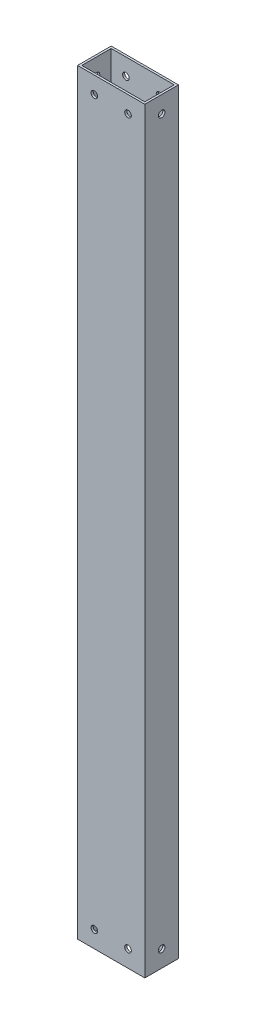
SolidWorks part; units mm, degrees
material "6061-T6 (SS)"
ref_plane "Front Plane" through (0, 0, 0) normal (0, 0, 1) x (1, 0, 0)
ref_plane "Top Plane" through (0, 0, 0) normal (0, 1, 0) x (1, 0, 0)
ref_plane "Right Plane" through (0, 0, 0) normal (1, 0, 0) x (0, 0, -1)
sketch "Sketch1" plane through (0, 0, 0) normal (0, 0, 1) x (1, 0, 0)
  line L1 (-25.4, -285.75) -> (25.4, -285.75)
  line L2 (-25.4, -285.75) -> (-25.4, 285.75)
  line L3 (-25.4, 285.75) -> (25.4, 285.75)
  line L4 (25.4, -285.75) -> (25.4, 285.75)
  line L5 (-25.4, -285.75) -> (25.4, 285.75) construction
  line L6 (-25.4, 285.75) -> (25.4, -285.75) construction
  point P0 (0, 0)
  dimension "D1" = 50.8
  dimension "D2" = 571.5
extrude "Boss-Extrude1" add sketch "Sketch1" along normal mid plane 25.4
shell "Shell1" thickness 1.5875 removed face at (0, -285.75, 0) removed face at (0, 285.75, 0)
sketch "Sketch2" plane through (0, 0, 0) normal (0, 0, 1) x (1, 0, 0)
  line L0 (-25.4, 285.75) -> (-25.4, -285.75) construction
  line L1 (-25.4, -285.75) -> (25.4, -285.75) construction
  line L2 (-25.4, 0) -> (25.4, 0) construction
  line L3 (25.4, -285.75) -> (25.4, 285.75) construction
  circle A0 centre (-12.7, -273.05) radius 2.4892
  circle A1 centre (12.7, -273.05) radius 2.4892
  circle A2 centre (12.7, 273.05) radius 2.4892
  circle A3 centre (-12.7, 273.05) radius 2.4892
  dimension "D1" = 4.9784
  dimension "D3" = 25.4
  dimension "D2" = 12.7
  dimension "D4" = 12.7
extrude "Cut-Extrude1" cut sketch "Sketch2" against normal through all both and the other way through all
sketch "Sketch3" plane through (0, 0, 0) normal (1, 0, 0) x (0, 0, -1)
  line L0 (-12.7, -285.75) -> (12.7, -285.75) construction
  line L1 (-12.7, 285.75) -> (12.7, 285.75) construction
  circle A0 centre (0, -273.05) radius 2.4892
  circle A1 centre (0, 273.05) radius 2.4892
  point P6 (0, -285.75)
  point P9 (0, 285.75)
  dimension "D1" = 4.9784
  dimension "D2" = 12.7
  dimension "D3" = 12.7
extrude "Cut-Extrude2" cut sketch "Sketch3" against normal through all both and the other way through all
